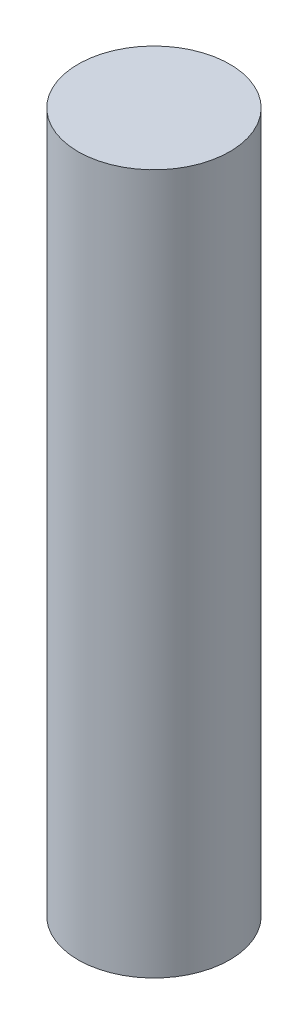
SolidWorks part; units mm, degrees
ref_plane "Front Plane" through (0, 0, 0) normal (0, 0, 1) x (1, 0, 0)
ref_plane "Top Plane" through (0, 0, 0) normal (0, 1, 0) x (1, 0, 0)
ref_plane "Right Plane" through (0, 0, 0) normal (1, 0, 0) x (0, 0, -1)
sketch "Sketch1" plane through (0, 0, 0) normal (0, 1, 0) x (1, 0, 0)
  circle A0 centre (0, 0) radius 32.5
  dimension "D1" = 65
extrude "Boss-Extrude1" add sketch "Sketch1" along normal blind 300
ref_plane "Plane1" through (0, 226.2, 0) normal (0, -1, 0) x (-1, 0, 0)
ref_plane "Plane3" through (0, 277, 0) normal (0, 1, 0) x (1, 0, 0)
ref_axis "Axis1" through (0, 300, 0) along (0, -1, 0)
ref_plane "Plane4" through (-32.5, 0, 0) normal (-1, 0, 0) x (0, 0, 1)
sketch "Sketch2" plane through (-32.5, 0, 0) normal (-1, 0, 0) x (0, 0, 1)
  line L0 (0, 277) -> (0, 226.2) construction
  line L1 (160.3535, 277) -> (-160.3535, 277) construction
  line L2 (0, 300) -> (0, 0) construction
  line L3 (-160.3535, 226.2) -> (160.3535, 226.2) construction
  line L5 (-7, 273.6) -> (7, 273.6)
  line L6 (-7, 273.6) -> (-7, 229.6)
  line L7 (-7, 229.6) -> (7, 229.6)
  line L8 (7, 273.6) -> (7, 229.6)
  line L9 (-7, 273.6) -> (7, 229.6) construction
  line L10 (-7, 229.6) -> (7, 273.6) construction
  point P8 (0, 251.6)
  dimension "D1" = 44
  dimension "D2" = 14
extrude "Cut-Extrude1" cut sketch "Sketch2" against normal blind 10
